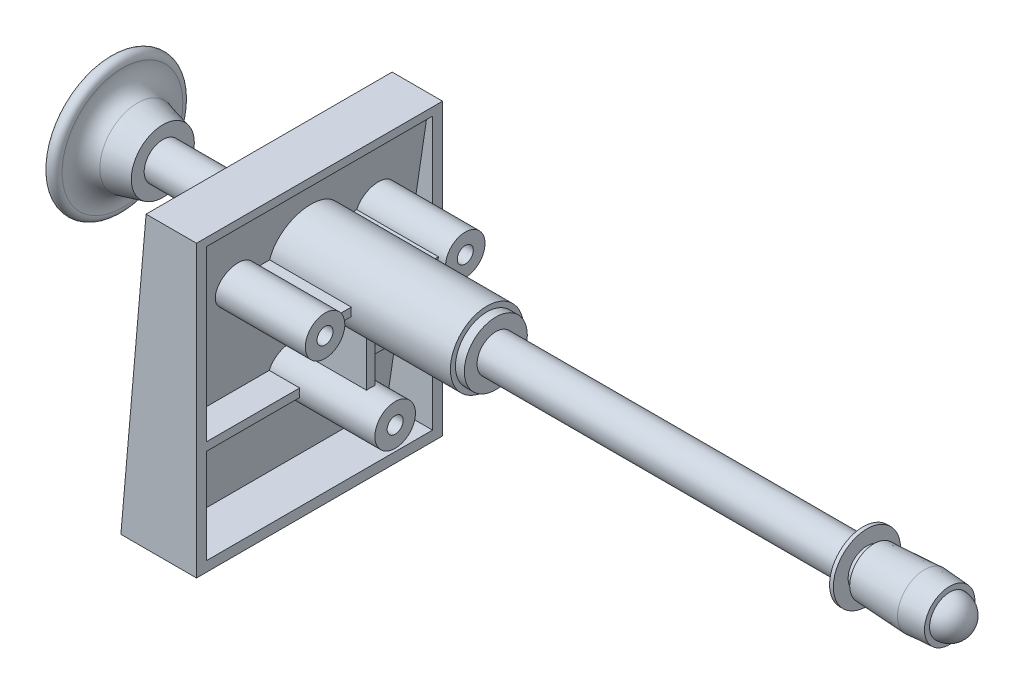
SolidWorks part; units mm, degrees
ref_plane "Front Plane" through (0, 0, 0) normal (0, 0, 1) x (1, 0, 0)
ref_plane "Top Plane" through (0, 0, 0) normal (0, 1, 0) x (1, 0, 0)
ref_plane "Right Plane" through (0, 0, 0) normal (1, 0, 0) x (0, 0, -1)
sketch "Sketch1" plane through (0, 0, 0) normal (1, 0, 0) x (0, 0, -1)
  line L1 (-30.988, 0) -> (30.988, 0)
  line L2 (-30.988, 0) -> (-30.988, 73.025)
  line L3 (-30.988, 73.025) -> (30.988, 73.025)
  line L4 (30.988, 0) -> (30.988, 73.025)
  point P4 (0, 0)
  dimension "D1" = 73.025
  dimension "D2" = 61.976
extrude "Boss-Extrude1" add sketch "Sketch1" against normal blind 19.05
sketch "Sketch2" plane through (0, 0, 30.988) normal (0, 0, 1) x (1, 0, 0)
  line L0 (0, 73.025) -> (-12.7, 73.025) construction
  line L1 (-19.05, 73.025) -> (0, 73.025) construction
  line L2 (-12.7, 73.025) -> (-19.05, 0)
  line L3 (-19.05, 0) -> (-19.05, 73.025)
  line L4 (-19.05, 73.025) -> (-12.7, 73.025)
  dimension "D1" = 6.35
extrude "Cut-Extrude1" cut sketch "Sketch2" against normal through all
sketch "Sketch4" plane through (-18.907, 1.6441, 0) normal (-0.9962, 0.0866, 0) x (0, 0, 1)
  line L0 (30.988, -1.6503) -> (-30.988, -1.6503) construction
  line L1 (-27.813, 68.4753) -> (27.813, 68.4753)
  line L2 (-27.813, 68.4753) -> (-27.813, 1.5247)
  line L3 (-27.813, 1.5247) -> (27.813, 1.5247)
  line L4 (27.813, 68.4753) -> (27.813, 1.5247)
  line L5 (30.988, -1.6503) -> (30.988, 71.6503) construction
  line L6 (-30.988, 71.6503) -> (30.988, 71.6503) construction
  point P4 (0, 1.5247)
  dimension "D1" = 3.175
  dimension "D2" = 3.175
  dimension "D3" = 3.175
extrude "Cut-Extrude3" cut sketch "Sketch4" against normal blind 3.175
sketch "Sketch3" plane through (0, 0, 0) normal (1, 0, 0) x (0, 0, -1)
  line L0 (-30.988, 73.025) -> (-30.988, 0) construction
  line L1 (-28.448, 71.0311) -> (28.448, 71.0311)
  line L2 (-28.448, 71.0311) -> (-28.448, 2.54)
  line L3 (-28.448, 2.54) -> (28.448, 2.54)
  line L4 (28.448, 71.0311) -> (28.448, 2.54)
  line L5 (-30.988, 0) -> (30.988, 0) construction
  line L6 (30.988, 73.025) -> (-30.988, 73.025) construction
  point P8 (0, 2.54)
  dimension "D1" = 2.54
  dimension "D2" = 2.54
  dimension "D3" = 1.9939
sketch3d "3DSketch1"
  line L0 (-11.5443, 2.54, 30.988) -> (-11.5443, 2.54, -30.988) construction
  line L6 (-1.27, 71.1327, 30.988) -> (-1.27, 71.1327, -30.988) construction
  dimension "D1" = 2.54
  dimension "D2" = 11.5443
  dimension "D3" = 1.8923
  dimension "D4" = 1.27
ref_plane "Plane1" through (-11.6631, 1.747, 0) normal (-0.989, 0.1481, 0) x (0, 0, 1)
extrude "Cut-Extrude5" cut sketch "Sketch3" against normal up to surface (1.2852 mm away) up to plane "Plane1"
sketch "Sketch9" plane through (0, 0, 0) normal (1, 0, 0) x (0, 0, -1)
  line L0 (-28.448, 71.0311) -> (-28.448, 2.54) construction
  line L1 (-28.448, 28.4607) -> (-5.0045, 28.4607)
  line L2 (-28.448, 28.4607) -> (-28.448, 26.3779)
  line L3 (-28.448, 26.3779) -> (-5.0045, 26.3779)
  line L4 (-5.0045, 28.4607) -> (-5.0045, 26.3779) construction
  line L5 (28.448, 2.54) -> (28.448, 71.0311) construction
  line L6 (28.448, 28.4607) -> (5.0045, 28.4607)
  line L7 (28.448, 28.4607) -> (28.448, 26.3779)
  line L8 (28.448, 26.3779) -> (5.0045, 26.3779)
  line L9 (5.0045, 28.4607) -> (5.0045, 26.3779) construction
  line L10 (-28.448, 2.54) -> (28.448, 2.54) construction
  line L11 (-28.448, 2.54) -> (28.448, 2.54) construction
  line L12 (-1.0414, 2.54) -> (1.0414, 2.54)
  line L13 (-1.0414, 2.54) -> (-1.0414, 22.4148) construction
  line L14 (-1.0414, 22.4148) -> (1.0414, 22.4148) construction
  line L15 (1.0414, 2.54) -> (1.0414, 22.4148) construction
  line L16 (0, 46.501) -> (0, 32.5311) construction
  line L17 (-1.0414, 46.5601) -> (1.0414, 46.5601) construction
  line L18 (-1.0414, 46.5601) -> (-1.0414, 32.4238) construction
  line L19 (-1.0414, 32.4238) -> (1.0414, 32.4238) construction
  line L20 (1.0414, 46.5601) -> (1.0414, 32.4238) construction
  line L22 (-9.1484, 56.7499) -> (-12.7976, 56.7499) construction
  line L23 (-9.1484, 56.7499) -> (-9.1484, 54.6672) construction
  line L24 (-9.1484, 54.6672) -> (-12.7976, 54.6672) construction
  line L25 (-12.7976, 56.7499) -> (-12.7976, 54.6672) construction
  line L26 (9.1484, 56.7499) -> (12.7976, 56.7499) construction
  line L27 (9.1484, 56.7499) -> (9.1484, 54.6672) construction
  line L28 (9.1484, 54.6672) -> (12.7976, 54.6672) construction
  line L29 (12.7976, 56.7499) -> (12.7976, 54.6672) construction
  line L31 (-12.6873, 55.7086) -> (-9.2075, 55.7086) construction
  arc A0 (-5.0045, 26.3779) -> (5.0045, 26.3779) centre (0, 27.4193) ccw
  circle A1 centre (0, 55.7086) radius 9.2075 construction
  circle A2 centre (-17.6593, 55.7086) radius 4.972 construction
  circle A3 centre (17.6593, 55.7086) radius 4.972 construction
  arc A6 (5.0045, 28.4607) -> (-5.0045, 28.4607) centre (0, 27.4193) ccw
  point P17 (0, 2.54)
  point P20 (-5.0045, 27.4193)
  point P32 (0, 32.4238)
  point P42 (-9.1484, 55.7086)
  point P43 (9.1484, 55.7086)
  line M24 (28.448, 71.0311) -> (28.448, 2.54)
  line M26 (-28.448, 2.54) -> (-28.448, 71.0311)
  dimension "D3" = 10.2235
  dimension "D4" = 18.415
  dimension "D7" = 9.9441
  dimension "D1" = 23.8379
  dimension "D2" = 2.0828
  dimension "D5" = 13.97
  dimension "D6" = 3.4798
extrude "Boss-Extrude2" add sketch "Sketch9" against normal up to surface (7.6617 mm away) contours L6 A6 L1 L3 A0 L8 M26 M24 region at (0, 27.4193, 0) up to face at (-6.4148, 36.7856, 0)
sketch "Sketch12" plane through (0, 0, 0) normal (1, 0, 0) x (0, 0, -1)
  circle A0 centre (0, 27.4193) radius 5.1117
  arc A2 (5.0045, 28.4607) -> (-5.0045, 28.4607) centre (0, 27.4193) ccw construction
extrude "Boss-Extrude4" add sketch "Sketch12" along normal blind 19.05
sketch "Sketch11" plane through (0, 0, 0) normal (1, 0, 0) x (0, 0, -1)
  line L0 (-1.0414, 46.5601) -> (-1.0414, 32.4238) construction
  line L1 (1.0414, 46.5601) -> (1.0414, 32.4238) construction
  line L2 (-1.0414, 46.5601) -> (-1.0414, 32.4238)
  line L3 (1.0414, 46.5601) -> (1.0414, 32.4238)
  line L4 (9.1484, 54.6672) -> (12.7976, 54.6672) construction
  line L5 (9.1484, 56.7499) -> (12.7976, 56.7499) construction
  line L6 (-9.1484, 54.6672) -> (-12.7976, 54.6672) construction
  line L7 (-9.1484, 56.7499) -> (-12.7976, 56.7499) construction
  line L8 (9.1484, 54.6672) -> (12.7976, 54.6672)
  line L9 (9.1484, 56.7499) -> (12.7976, 56.7499)
  line L10 (-9.1484, 54.6672) -> (-12.7976, 54.6672)
  line L11 (-9.1484, 56.7499) -> (-12.7976, 56.7499)
  circle A0 centre (0, 55.7086) radius 9.2075 construction
  arc A1 (5.0045, 28.4607) -> (-5.0045, 28.4607) centre (0, 27.4193) ccw construction
  arc A2 (1.0414, 46.5601) -> (9.1484, 54.6672) centre (0, 55.7086) ccw
  arc A3 (1.0414, 32.4238) -> (-1.0414, 32.4238) centre (0, 27.4193) ccw
  circle A4 centre (17.6593, 55.7086) radius 4.972 construction
  circle A5 centre (-17.6593, 55.7086) radius 4.972 construction
  arc A6 (12.7976, 54.6672) -> (12.7976, 56.7499) centre (17.6593, 55.7086) ccw
  arc A7 (-12.7976, 56.7499) -> (-12.7976, 54.6672) centre (-17.6593, 55.7086) ccw
  arc A8 (-9.1484, 54.6672) -> (-1.0414, 46.5601) centre (0, 55.7086) ccw
  arc A9 (9.1484, 56.7499) -> (-9.1484, 56.7499) centre (0, 55.7086) ccw
extrude "Boss-Extrude3" add sketch "Sketch11" against normal up to surface and the other way blind 19.05 up to face at (-5.4346, 43.3292, 0)
sketch "Sketch13" plane through (19.05, 0, 0) normal (1, 0, 0) x (0, 0, -1)
  line L0 (-1.0414, 46.5601) -> (-1.0414, 32.4238) construction
  line L1 (-1.0414, 46.5601) -> (-1.0414, 32.4238)
  line L2 (1.0414, 46.5601) -> (1.0414, 32.4238) construction
  line L3 (1.0414, 46.5601) -> (1.0414, 32.4238)
  arc A0 (5.0045, 28.4607) -> (-5.0045, 28.4607) centre (0, 27.4193) ccw construction
  circle A1 centre (0, 55.7086) radius 9.2075 construction
  arc A2 (1.0414, 32.4238) -> (-1.0414, 32.4238) centre (0, 27.4193) ccw
  arc A3 (-1.0414, 46.5601) -> (1.0414, 46.5601) centre (0, 55.7086) ccw
extrude "Cut-Extrude6" cut sketch "Sketch13" against normal blind 6.1214
sketch "Sketch14" plane through (19.05, 0, 0) normal (1, 0, 0) x (0, 0, -1)
  line L0 (-9.1484, 54.6672) -> (-12.7976, 54.6672) construction
  line L1 (-9.1484, 56.7499) -> (-12.7976, 56.7499) construction
  line L2 (-9.1484, 54.6672) -> (-12.7976, 54.6672)
  line L3 (-9.1484, 56.7499) -> (-12.7976, 56.7499)
  line L4 (9.1484, 54.6672) -> (12.7976, 54.6672) construction
  line L5 (9.1484, 56.7499) -> (12.7976, 56.7499) construction
  line L6 (9.1484, 54.6672) -> (12.7976, 54.6672)
  line L7 (9.1484, 56.7499) -> (12.7976, 56.7499)
  circle A0 centre (0, 55.7086) radius 9.2075 construction
  circle A1 centre (-17.6593, 55.7086) radius 4.972 construction
  arc A2 (-9.1484, 56.7499) -> (-9.1484, 54.6672) centre (0, 55.7086) ccw
  arc A3 (-12.7976, 54.6672) -> (-12.7976, 56.7499) centre (-17.6593, 55.7086) ccw
  circle A4 centre (17.6593, 55.7086) radius 4.972 construction
  arc A5 (12.7976, 56.7499) -> (12.7976, 54.6672) centre (17.6593, 55.7086) ccw
  arc A6 (9.1484, 54.6672) -> (9.1484, 56.7499) centre (0, 55.7086) ccw
extrude "Cut-Extrude7" cut sketch "Sketch14" against normal blind 1.905
sketch "Sketch15" plane through (19.05, 0, 0) normal (1, 0, 0) x (0, 0, -1)
  circle A1 centre (0, 55.7086) radius 9.2075
  circle A2 centre (0, 55.7086) radius 9.2075
  dimension "D1" = 0
extrude "Boss-Extrude5" add sketch "Sketch15" along normal offset from surface (23.114 mm away) 23.114 up to face at (19.05, 55.7086, -9.2075) offset beyond the face yes
sketch "Sketch16" plane through (42.164, 0, 0) normal (1, 0, 0) x (0, 0, -1)
  circle A0 centre (0, 55.7086) radius 7.9375
  dimension "D1" = 15.875
extrude "Boss-Extrude6" add sketch "Sketch16" along normal blind 2.2352
hole_wizard "#10-32 Tapped Hole1" positions "Sketch21" profile "Sketch23" tap size "#10-32" standard "ANSI Inch"
sketch "Sketch21" plane through (19.05, 0, 0) normal (1, 0, 0) x (0, 0, -1)
  point P0 (-17.6593, 55.7086)
  point P3 (17.6593, 55.7086)
  point P6 (0, 27.4193)
sketch "Sketch23" plane through (19.05, 55.7086, 17.6593) normal (0, 1, 0) x (0, 0, -1)
  line L0 (0, 0) -> (0, 24.0733)
  line L1 (0, 24.0733) -> (2.0193, 22.86)
  line L2 (2.0193, 22.86) -> (2.0193, 0)
  line L5 (2.0193, 0) -> (0, 0)
  line L10 (0, 24.0733) -> (-2.0193, 22.86) construction
  line L11 (0, -6.35) -> (0, 107.95) construction
  dimension "Tap Drill Dia." = 4.0386
  dimension "Tap Drill Depth" = 22.86
  dimension "Drill Angle" = 118
cosmetic thread "Hole Thread1" parameters "D1"=9.652, "D2"=4.826
cosmetic thread "Hole Thread2" parameters "D1"=9.652, "D2"=4.826
cosmetic thread "Hole Thread3" parameters "D1"=9.652, "D2"=4.826
sketch "Sketch17" plane through (44.3992, 0, 0) normal (1, 0, 0) x (0, 0, -1)
  circle A0 centre (0, 55.7086) radius 4.7308
  dimension "D1" = 9.4615
extrude "Boss-Extrude7" add sketch "Sketch17" along normal blind 95.25
sketch "Sketch18" plane through (0, 0, 0) normal (0, 0, 1) x (1, 0, 0)
  line L0 (139.6492, 55.7086) -> (163.7792, 55.7086)
  line L1 (139.6492, 50.9778) -> (139.6492, 60.4393) construction
  line L2 (139.6492, 55.7086) -> (139.6492, 61.83)
  line L3 (139.6492, 61.83) -> (152.3683, 62.5031)
  line L4 (152.3683, 62.5031) -> (158.7183, 62.0586)
  line L5 (158.7183, 62.0586) -> (158.7183, 60.7695)
  line L6 (163.7792, 55.7086) -> (163.7792, 49.343) construction
  line L7 (158.7183, 60.7695) -> (139.6492, 60.7695) construction
  arc A0 (163.7792, 55.7086) -> (158.7183, 60.7695) centre (158.7183, 55.7086) ccw
  dimension "D1" = 6.1214
  dimension "D2" = 5.061
  dimension "D3" = 6.35
  dimension "D4" = 6.7945
  dimension "D5" = 6.35
  dimension "D6" = 24.13
revolve "Revolve1" add sketch "Sketch18" angle 360 about L0
ref_plane "Plane2" through (137.8712, 0, 0) normal (-1, 0, 0) x (0, 0, 1)
sketch "Sketch19" plane through (137.8712, 0, 0) normal (-1, 0, 0) x (0, 0, 1)
  circle A0 centre (0, 55.7086) radius 8.4582
  dimension "D1" = 16.9164
extrude "Boss-Extrude8" add sketch "Sketch19" along normal blind 0.9525
ref_plane "Plane3" through (-19.05, 0, 0) normal (1, 0, 0) x (0, 0, -1)
sketch "Sketch24" plane through (-19.05, 0, 0) normal (1, 0, 0) x (0, 0, -1)
  circle A0 centre (0, 55.7086) radius 9.2075
  circle A1 centre (0, 55.7086) radius 9.2075 construction
extrude "Boss-Extrude9" add sketch "Sketch24" along normal up to surface (8.0312 mm away) up to face at (-12.7119, 36.2375, 0)
sketch "Sketch25" plane through (-19.05, 0, 0) normal (-1, 0, 0) x (0, 0, 1)
  circle A0 centre (0, 55.7086) radius 7.9375
  dimension "D1" = 15.875
extrude "Boss-Extrude10" add sketch "Sketch25" along normal blind 1.3716
sketch "Sketch26" plane through (-20.4216, 0, 0) normal (-1, 0, 0) x (0, 0, 1)
  circle A0 centre (0, 55.7086) radius 4.6926
  dimension "D1" = 9.3853
extrude "Boss-Extrude11" add sketch "Sketch26" along normal blind 19.05
sketch "Sketch27" plane through (0, 0, 0) normal (0, 0, 1) x (1, 0, 0)
  line L0 (-39.4716, 55.7086) -> (-58.5216, 55.7086)
  line L1 (-39.4716, 60.4012) -> (-39.4716, 51.0159) construction
  line L2 (-39.4716, 55.7086) -> (-39.4716, 63.6461)
  line L5 (-52.6798, 71.8066) -> (-57.2516, 61.633)
  line L6 (-58.5216, 55.7086) -> (-58.5216, 50.2426) construction
  line L7 (-45.8216, 65.2336) -> (-39.4716, 63.6461)
  arc A1 (-49.6316, 70.9182) -> (-52.6798, 71.8066) centre (-51.2177, 71.1496) ccw
  arc A2 (-58.5216, 55.7086) -> (-57.2516, 61.633) centre (-44.0681, 55.7086) cw
  arc A3 (-49.6316, 70.9182) -> (-45.8216, 65.2336) centre (-44.5845, 70.1818) ccw
  point P30 (-50.7692, 72.6885)
  dimension "D1" = 19.05
  dimension "D2" = 7.9375
  dimension "D3" = 9.525
  dimension "D4" = 3.175
  dimension "D5" = 10.16
  dimension "D6" = 6.35
  dimension "D7" = 17.78
  dimension "D8" = 16.9799
revolve "Revolve2" add sketch "Sketch27" angle 360 about L0
sketch "Sketch28" plane through (0, 0, 0) normal (0, 0, 1) x (1, 0, 0)
  line L0 (163.7792, 55.7086) -> (44.3992, 55.7086) construction
  line L1 (44.3992, 50.9778) -> (44.3992, 60.4393) construction
  arc A0 (158.7183, 50.6476) -> (158.7183, 60.7695) centre (158.7183, 55.7086) ccw construction
ref_plane "Plane4" through (0, 55.7086, 0) normal (0, 1, 0) x (-1, 0, 0)
